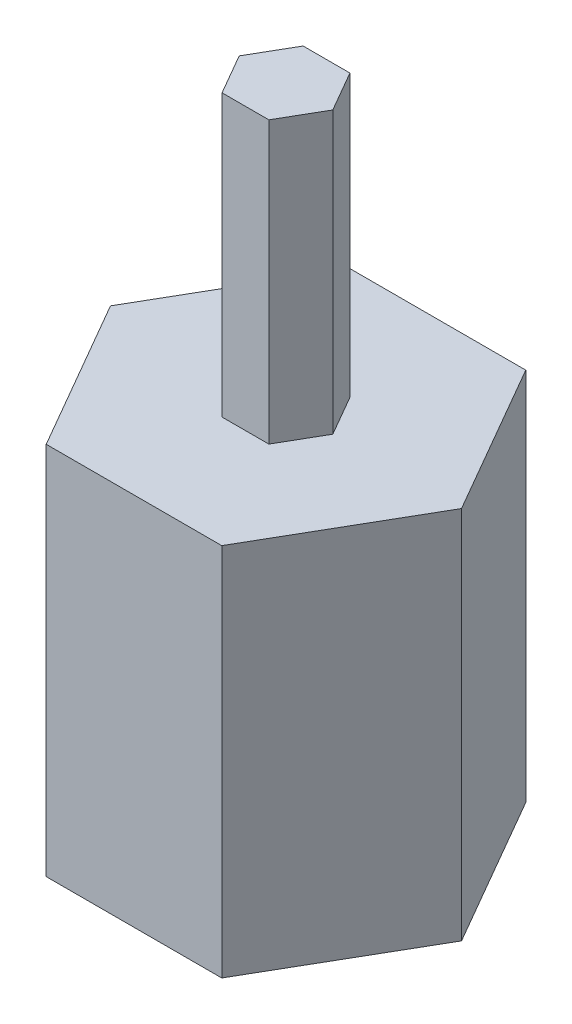
SolidWorks part; units mm, degrees
ref_plane "Front Plane" through (0, 0, 0) normal (0, 0, 1) x (1, 0, 0)
ref_plane "Top Plane" through (0, 0, 0) normal (0, 1, 0) x (1, 0, 0)
ref_plane "Right Plane" through (0, 0, 0) normal (1, 0, 0) x (0, 0, -1)
sketch "Sketch1" plane through (0, 0, 0) normal (0, 1, 0) x (1, 0, 0)
  line L1 (1, 0) -> (0.5, 0.866)
  line L2 (0.5, 0.866) -> (-0.5, 0.866)
  line L3 (-0.5, 0.866) -> (-1, 0)
  line L4 (-1, 0) -> (-0.5, -0.866)
  line L5 (-0.5, -0.866) -> (0.5, -0.866)
  line L6 (0.5, -0.866) -> (1, 0)
  circle A0 centre (0, 0) radius 0.866 construction
  dimension "D1" = 1
extrude "Boss-Extrude1" add sketch "Sketch1" along normal blind 6
sketch "Sketch2" plane through (0, 0, 0) normal (0, -1, 0) x (1, 0, 0)
  line L1 (3.75, 0) -> (1.875, 3.2476)
  line L2 (1.875, 3.2476) -> (-1.875, 3.2476)
  line L3 (-1.875, 3.2476) -> (-3.75, 0)
  line L4 (-3.75, 0) -> (-1.875, -3.2476)
  line L5 (-1.875, -3.2476) -> (1.875, -3.2476)
  line L6 (1.875, -3.2476) -> (3.75, 0)
  circle A0 centre (0, 0) radius 3.2476 construction
  circle A1 centre (0, 0) radius 3.75 construction
  dimension "D1" = 7.5
extrude "Boss-Extrude2" add sketch "Sketch2" along normal blind 8
